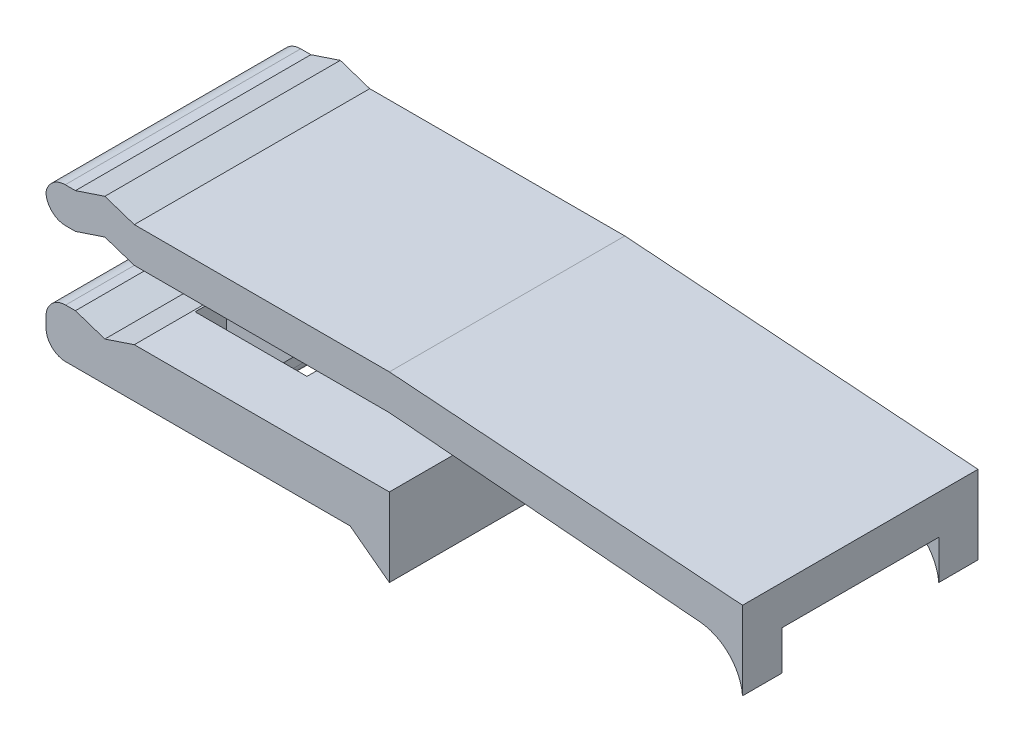
SolidWorks part; units mm, degrees
ref_plane "Front Plane" through (0, 0, 0) normal (0, 0, 1) x (1, 0, 0)
ref_plane "Top Plane" through (0, 0, 0) normal (0, 1, 0) x (1, 0, 0)
ref_plane "Right Plane" through (0, 0, 0) normal (1, 0, 0) x (0, 0, -1)
sketch "Sketch1" plane through (0, 0, 0) normal (0, 0, 1) x (1, 0, 0)
  line L0 (0, 0) -> (0, 4) construction
  line L1 (0, 0) -> (-18, 0) construction
  line L2 (0, 4) -> (-18, 5.3)
  line L3 (-18, 5.3) -> (-31, 5.3)
  line L4 (-31, 5.3) -> (-32.5, 5.8)
  line L5 (-32.5, 5.8) -> (-34, 5.3)
  line L6 (-34, 5.3) -> (-35.5, 5.3)
  line L7 (-35.5, 5.3) -> (-35.5, 3.5)
  line L8 (-35.5, -2.5) -> (-20, -2.5)
  line L9 (-20, -2.5) -> (-18, -4)
  line L10 (-35.5, 3.5) -> (-34, 3.5)
  line L11 (-34, 3.5) -> (-32.5, 4)
  line L12 (-18, 0) -> (-18, -4)
  line L13 (-18, 0) -> (-31, 0)
  line L14 (-31, 0) -> (-32.5, -0.5)
  line L15 (-32.5, -0.5) -> (-34, 0)
  line L16 (-34, 0) -> (-35.5, 0)
  line L17 (-35.5, 0) -> (-35.5, -2.5)
  line L18 (-32.5, 4) -> (-31, 3.5)
  line L19 (-31, 3.5) -> (-18, 3.5)
  line L20 (-18, 0) -> (-18, 5.3) construction
  line L21 (-18, 3.5) -> (0, 2)
  line L22 (0, 2) -> (0, 4)
  dimension "D1" = 13
  dimension "D2" = 18
  dimension "D3" = 0.5
  dimension "D4" = 2.5
  dimension "D5" = 1.5
  dimension "D6" = 3.5
  dimension "D7" = 1.5
  dimension "D8" = 2
  dimension "D9" = 0.5
  dimension "D10" = 2
  dimension "D11" = 0.5
  dimension "D12" = 1.8
  dimension "D13" = 1.5
  dimension "D15" = 3
  dimension "D16" = 1.5
extrude "Boss-Extrude1" add sketch "Sketch1" along normal blind 12
sketch "Sketch2" plane through (0, -2.5, 0) normal (0, -1, 0) x (1, 0, 0)
  line L0 (-20, 12) -> (-20, 0) construction
  line L1 (-30.9, 9) -> (-25.2, 9)
  line L2 (-30.9, 9) -> (-30.9, 3)
  line L3 (-30.9, 3) -> (-25.2, 3)
  line L4 (-25.2, 9) -> (-25.2, 3)
  line L5 (-31, 12) -> (-31, 0) construction
  line L7 (-20, 6) -> (-35.5, 6) construction
  line L8 (-35.5, 12) -> (-35.5, 0) construction
  point P9 (-25.2, 6)
  dimension "D1" = 0.1
  dimension "D2" = 5.7
  dimension "D3" = 6
extrude "Cut-Extrude1" cut sketch "Sketch2" against normal blind 3
sketch "Sketch3" plane through (0, 0, 3) normal (0, 0, 1) x (1, 0, 0)
  line L0 (-25.2, 0) -> (-27.2, -2)
  line L1 (-27.2, -2) -> (-27.2, -2.5)
  line L2 (-35.5, -2.5) -> (-20, -2.5) construction
  line L3 (-27.2, -2.5) -> (-25.2, -2.5)
  line L4 (-25.2, -2.5) -> (-25.2, 0)
  dimension "D1" = 0.5
  dimension "D2" = 2
extrude "Boss-Extrude2" add sketch "Sketch3" along normal up to surface (6 mm away) up to face at (-28.05, -1.25, 9)
sketch "Sketch4" plane through (0, 0, 12) normal (0, 0, 1) x (1, 0, 0)
  line L0 (-28.4, -2) -> (-26.4, 0)
  line L1 (-18, 0) -> (-31, 0) construction
  line L2 (-26.4, 0) -> (-26.4, 0.4)
  line L3 (-26.4, 0.4) -> (-27.9, 0.4)
  line L4 (-27.9, 0.4) -> (-27.9, 1.9)
  line L5 (-31, 3.5) -> (-18, 3.5) construction
  line L6 (-28.4, -2) -> (-28.4, -3)
  line L7 (-28.4, -3) -> (-29.8, -3)
  line L8 (-29.8, -3) -> (-29.8, 3.5)
  line L9 (-29.8, 3.5) -> (-26.3, 3.5)
  line L10 (-27.2, -2) -> (-27.2, -2.5) construction
  line L11 (-30.9, 0) -> (-30.9, -2.5) construction
  line L15 (-35.5, -2.5) -> (-20, -2.5) construction
  arc A1 (-27.9, 1.9) -> (-26.3, 3.5) centre (-26.3, 1.9) cw
  dimension "D1" = 1.5
  dimension "D2" = 1.2
  dimension "D3" = 45
  dimension "D4" = 0.4
  dimension "D5" = 1.4
  dimension "D6" = 1
  dimension "D7" = 2
  dimension "D8" = 1.5
  dimension "D9" = 1.1
  dimension "D11" = 0.8
  dimension "D13" = 2.9
  dimension "D14" = 3.1
extrude "Boss-Extrude3" add sketch "Sketch4" against normal mid plane 5 from offset 6 offset against normal yes
fillet "Fillet7" radius 1 1 edges at (-35.5, 0, 6)
fillet "Fillet8" radius 1 1 edges at (-35.5, 3.5, 6)
fillet "Fillet10" radius 1 1 edges at (-35.5, 5.3, 6)
fillet "Fillet11" radius 1 1 edges at (-35.5, -2.5, 6)
sketch "Sketch5" plane through (0, 0, 12) normal (0, 0, 1) x (1, 0, 0)
  line L0 (0, 2) -> (0, 0)
  line L1 (-18, 3.5) -> (0, 2) construction
  line L2 (-2.1818, 2.1818) -> (0, 2)
  arc A0 (-2.1818, 2.1818) -> (0, 0) centre (-2.3802, -0.1983) cw
extrude "Boss-Extrude4" add sketch "Sketch5" against normal blind 2
extrude "Boss-Extrude5" add sketch "Sketch5<2>" along normal blind 2 from offset 12 offset against normal yes
sketch "Sketch5<2>" plane through (0, 0, 12) normal (0, 0, 1) x (1, 0, 0) same geometry as "Sketch5"
fillet "Fillet12" radius 0.5 2 edges at (-28.4, -3, 6) (-29.8, -3, 6)
